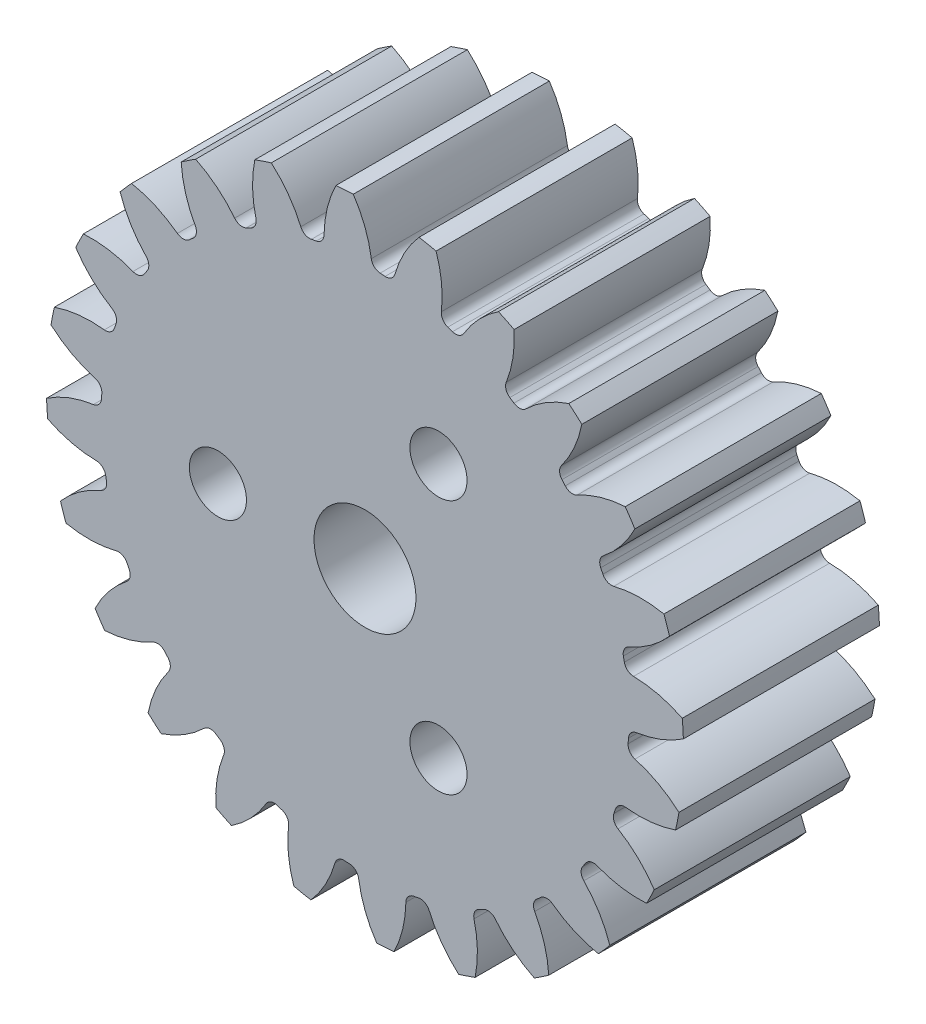
SolidWorks part; units mm, degrees
ref_plane "Front" through (0, 0, 0) normal (0, 0, 1) x (1, 0, 0)
ref_plane "Top" through (0, 0, 0) normal (0, 1, 0) x (1, 0, 0)
ref_plane "Right" through (0, 0, 0) normal (1, 0, 0) x (0, 0, -1)
sketch "Sketch3" plane through (0, 0, 0) normal (0, 0, 1) x (1, 0, 0)
  circle A0 centre (0, 0) radius 20.6375
  dimension "od" = 41.275
extrude "gearBody" add sketch "Sketch3" along normal blind 12.7
sketch "Sketch2" plane through (0, 0, 0) normal (0, 0, 1) x (1, 0, 0)
  line L0 (0, 0) -> (16.5385, 6.8505) construction
  line L1 (22.0347, -5.709) -> (0, 0) construction
  line L2 (0, 0) -> (36.3143, 0) construction
  line L3 (19.05, -0.043) -> (18.8852, -2.5004) construction
  line L5 (18.9676, -1.2717) -> (0, 0) construction
  line L7 (0, 0) -> (17.9011, 0) construction
  arc A0 (17.8975, -0.3593) -> (17.7853, -2.0332) centre (0, 0) ccw construction
  arc A1 (20.6236, 0.7563) -> (20.3381, -3.5027) centre (0, 0) ccw construction
  arc A2 (19.05, -0.043) -> (18.8852, -2.5004) centre (0, 0) ccw construction
  arc A3 (17.0444, -1.304) -> (17.0659, -0.983) centre (0, 0) ccw
  arc A4 (22.0347, -5.709) -> (17.4884, -1.9416) centre (15.476, -8.9969) ccw
  arc A5 (22.0347, -5.709) -> (22.5996, 2.7164) centre (0, 0) ccw
  arc A6 (22.5996, 2.7164) -> (17.5911, -0.4103) centre (16.5385, 6.8505) cw
  arc A7 (17.0659, -0.983) -> (17.5911, -0.4103) centre (17.6793, -1.0183) cw
  arc A8 (17.4884, -1.9416) -> (17.0444, -1.304) centre (17.657, -1.3509) cw
  point P6 (22.5996, 2.7164)
  point P22 (22.0347, -5.709)
  dimension "baseDia" = 35.8023
  dimension "od" = 41.275
  dimension "pd" = 38.1
  dimension "rd" = 34.1884
  dimension "rFillet" = 0.6144
  dimension "pointX" = 22.5996
  dimension "pointY" = 2.7164
  dimension "CTT" = 2.4574
  dimension "flankCenterAngle" = 22.5
extrude "toothCut" cut sketch "Sketch2" along normal through all
pattern_circular "CirPattern1" count 24 over 360 about axis through (0, 0, 12.7) along (0, 0, -1) of "toothCut"
sketch "hub1Dia" plane through (0, 0, 0) normal (0, 0, -1) x (-1, 0, 0)
  circle A0 centre (0, 0) radius 12.7
  dimension "hub1Dia" = 25.4
sketch "hub2Dia" plane through (0, 0, 12.7) normal (0, 0, 1) x (1, 0, 0)
  circle A0 centre (0, 0) radius 12.7
  dimension "hub2dia" = 25.4
sketch "boreDia" plane through (0, 0, 0) normal (0, 0, 1) x (1, 0, 0)
  circle A0 centre (0, 0) radius 6.35
  dimension "boreDia" = 12.7
sketch "Sketch4" plane through (0, 0, 0) normal (0, 0, -1) x (-1, 0, 0)
  circle A0 centre (9.525, 0) radius 1.85
  circle A1 centre (-4.7625, -8.2489) radius 1.85
  circle A2 centre (-4.7625, 8.2489) radius 1.85
  point P9 (0, 0)
  dimension "D2" = 3.7
  dimension "D1" = 9.525
  dimension "D3" = 3
extrude "Cut-Extrude1" cut sketch "Sketch4" against normal through all
sketch "Sketch5" plane through (0, 0, 0) normal (0, 0, -1) x (-1, 0, 0)
  circle A0 centre (0, 0) radius 3.302
  dimension "D1" = 6.604
extrude "Cut-Extrude2" cut sketch "Sketch5" against normal through all
equation "\"D2@Sketch4\"=3.7mm"
equation "\"D1@Sketch5\" = \"normTol\" + 0.25"
equation "\"tightTol\" = 0.005in"
equation "\"normTol\"= 0.01in"
equation "\"looseTol\"= 0.02in"
